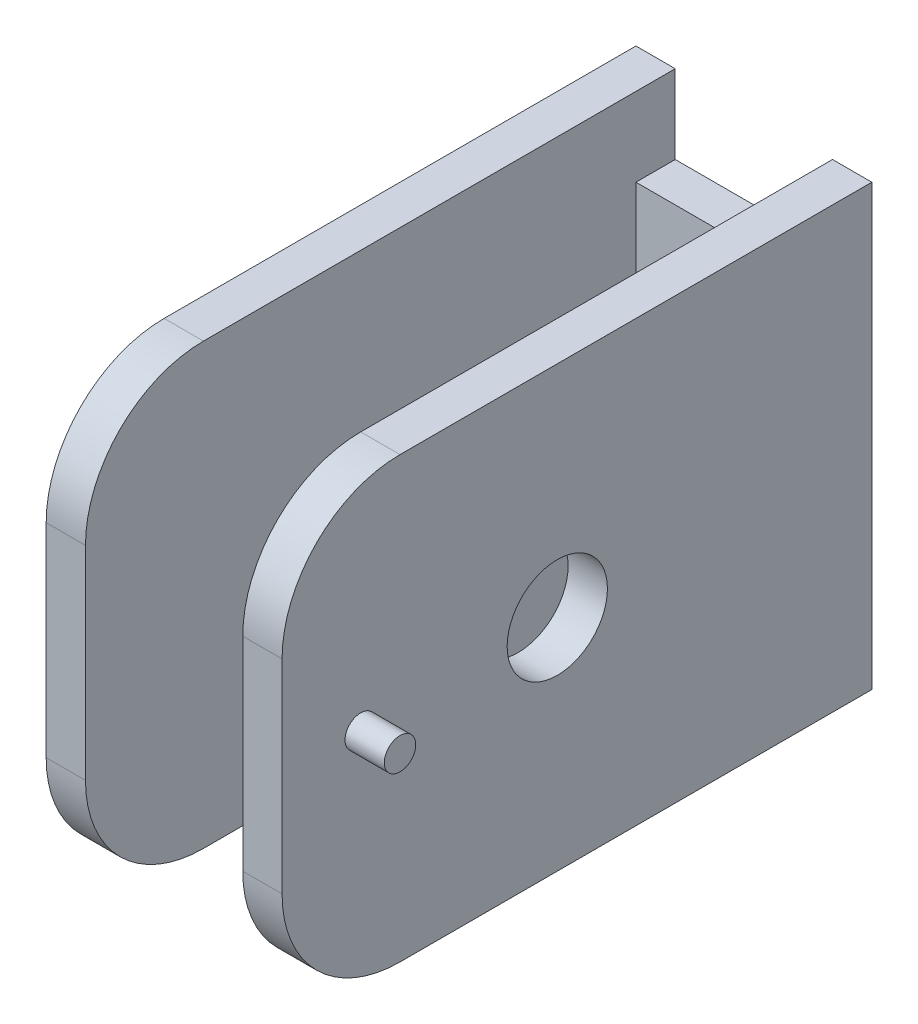
SolidWorks part; units mm, degrees
ref_plane "Front Plane" through (0, 0, 0) normal (0, 0, 1) x (1, 0, 0)
ref_plane "Top Plane" through (0, 0, 0) normal (0, 1, 0) x (1, 0, 0)
ref_plane "Right Plane" through (0, 0, 0) normal (1, 0, 0) x (0, 0, -1)
sketch "Sketch1" plane through (0, 0, 0) normal (0, 1, 0) x (1, 0, 0)
  line L0 (-7.5, -17.5) -> (-7.5, 20)
  line L2 (-5, -17.5) -> (-5, 17.5)
  line L3 (-5, 17.5) -> (5, 17.5)
  line L4 (5, -17.5) -> (5, 17.5)
  line L5 (-5, -17.5) -> (5, 17.5) construction
  line L6 (-5, 17.5) -> (5, -17.5) construction
  line L7 (-7.5, 20) -> (7.5, 20)
  line L8 (7.5, -17.5) -> (7.5, 20)
  line L10 (-5, -17.5) -> (-7.5, -17.5)
  line L11 (5, -17.5) -> (7.5, -17.5)
  line L12 (7.5, -20) -> (7.5, 20) construction
  line L13 (-7.5, -20) -> (7.5, -20) construction
  line L14 (-7.5, -20) -> (-7.5, 20) construction
  line L15 (-5, -17.5) -> (5, -17.5) construction
  point P0 (0, 0)
  dimension "D1" = 10
  dimension "D2" = 35
  dimension "D3" = 2.5
extrude "Boss-Extrude1" add sketch "Sketch1" along normal mid plane 27.94
sketch "Sketch4" plane through (5, 0, 0) normal (-1, 0, 0) x (0, 0, 1)
  line L1 (-20, 13.97) -> (-20, -13.97) construction
  line L2 (0, 13.97) -> (0, -13.97) construction
  line L3 (-20, 13.97) -> (17.5, 13.97) construction
  line L4 (-20, -13.97) -> (17.5, -13.97) construction
  circle A0 centre (0, 0) radius 3.1877
  point P9 (0, 0)
  point P10 (0, 0)
  point P11 (0, 3.1839)
  dimension "D1" = 6.3754
  dimension "D3" = 20
sketch "Sketch5" plane through (7.5, 0, 0) normal (1, 0, 0) x (0, 0, -1)
  line L1 (-17.5, 13.97) -> (-17.5, -13.97) construction
  circle A0 centre (-12.5, 0) radius 1
  point P2 (-17.5, 0)
  dimension "D1" = 2
  dimension "D3" = 5
extrude "Boss-Extrude4" add sketch "Sketch5" along normal blind 2.5
sketch "Sketch6" plane through (0, 0, -20) normal (0, 0, -1) x (-1, 0, 0)
  line L0 (-7.5, -13.97) -> (7.5, -13.97) construction
  line L1 (5, -8.97) -> (-5, -8.97)
  line L2 (5, -8.97) -> (5, -13.97)
  line L3 (5, -13.97) -> (-5, -13.97)
  line L4 (-5, -8.97) -> (-5, -13.97)
  line L5 (5, -8.97) -> (-5, -13.97) construction
  line L6 (5, -13.97) -> (-5, -8.97) construction
  point P0 (0, -11.47)
  dimension "D1" = 10
  dimension "D2" = 5
extrude "Cut-Extrude1" cut sketch "Sketch6" against normal up to next
fillet "Fillet1" radius 7.5 4 edges at (-6.25, -13.97, 17.5) (-6.25, 13.97, 17.5) (6.25, -13.97, 17.5) (6.25, 13.97, 17.5)
extrude "Cut-Extrude2" cut sketch "Sketch4" along normal through all both and the other way through all
mirror "Mirror1" about plane through (0, 0, 0) normal (1, 0, 0) of "Boss-Extrude4"
mirror "Mirror2" about plane through (0, 0, 0) normal (0, 1, 0) of "Cut-Extrude1"
